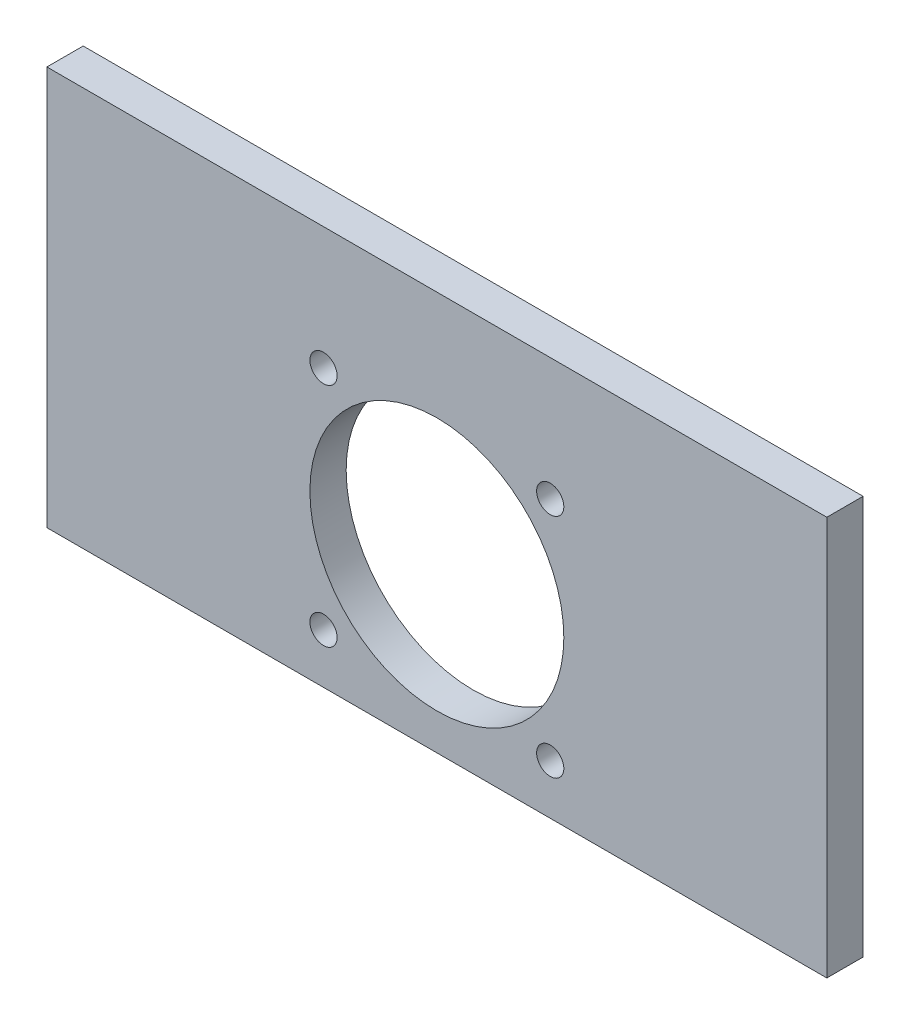
SolidWorks part; units mm, degrees
ref_plane "Płaszczyzna przednia" through (0, 0, 0) normal (0, 0, 1) x (1, 0, 0)
ref_plane "Płaszczyzna górna" through (0, 0, 0) normal (0, 1, 0) x (1, 0, 0)
ref_plane "Płaszczyzna prawa" through (0, 0, 0) normal (1, 0, 0) x (0, 0, -1)
sketch "Sketch1" plane through (0, 0, 0) normal (0, 0, 1) x (1, 0, 0)
  line L1 (0, 0) -> (86, 0)
  line L2 (0, 0) -> (0, 44)
  line L3 (0, 44) -> (86, 44)
  line L4 (86, 0) -> (86, 44)
  line L5 (0, 0) -> (86, 44) construction
  line L6 (0, 44) -> (86, 0) construction
  point P4 (43, 22)
  dimension "D1" = 86
  dimension "D2" = 44
extrude "Boss-Extrude1" add sketch "Sketch1" along normal blind 4
sketch "Sketch2" plane through (0, 0, 4) normal (0, 0, 1) x (1, 0, 0)
  line L0 (86, 44) -> (0, 44) construction
  line L1 (86, 0) -> (86, 44) construction
  circle A0 centre (43, 18) radius 14
  dimension "D1" = 28
  dimension "D2" = 26
  dimension "D3" = 43
extrude "Cut-Extrude1" cut sketch "Sketch2" against normal blind 4
sketch "Sketch3" plane through (0, 0, 4) normal (0, 0, 1) x (1, 0, 0)
  line L1 (28, 33) -> (58, 33) construction
  line L2 (28, 33) -> (28, 3) construction
  line L3 (28, 3) -> (58, 3) construction
  line L4 (58, 33) -> (58, 3) construction
  line L5 (28, 33) -> (58, 3) construction
  line L6 (28, 3) -> (58, 33) construction
  circle A0 centre (43, 18) radius 14 construction
  circle A1 centre (30.5, 30.5) radius 1.5
  circle A5 centre (55.5, 30.5) radius 1.5
  circle A6 centre (55.5, 5.5) radius 1.5
  circle A7 centre (30.5, 5.5) radius 1.5
  point P4 (43, 18)
  dimension "D4" = 3
  dimension "D5" = 2.5
  dimension "D6" = 2.5
  dimension "D1" = 30
  dimension "D2" = 15
  dimension "D3" = 15
  dimension "D7" = 4
extrude "Cut-Extrude3" cut sketch "Sketch3" against normal blind 4
